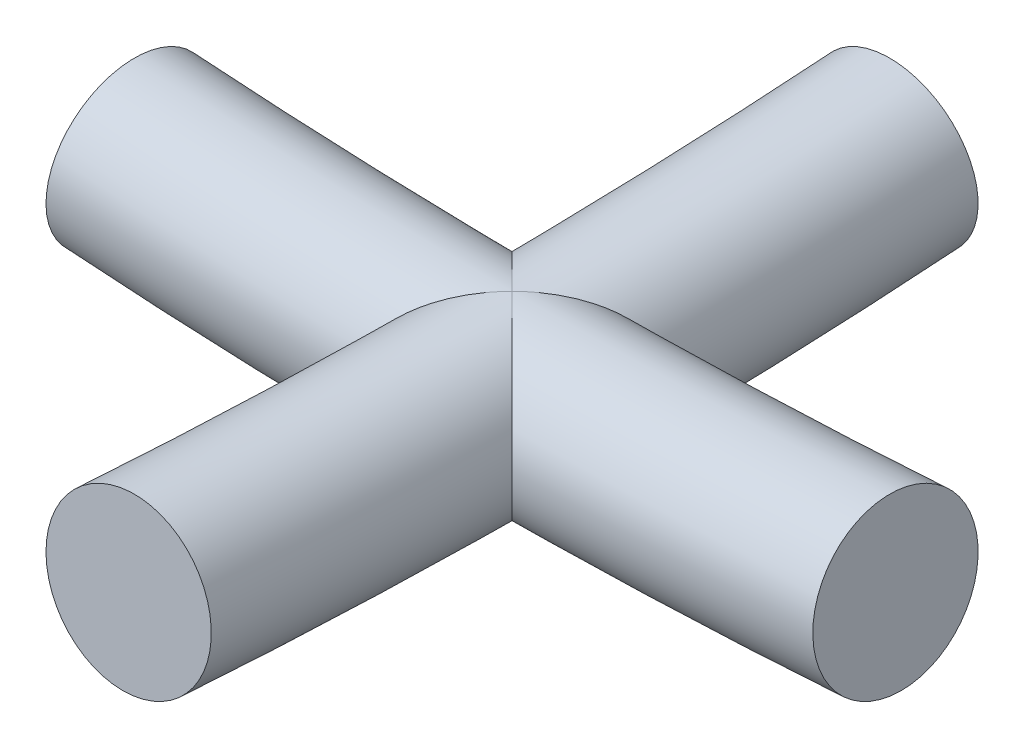
SolidWorks part; units mm, degrees
note: '?' marks a value the reader was unsure of.
ref_plane "Front Plane" through (0, 0, 0) normal (0, 0, 1) x (1, 0, 0)
ref_plane "Top Plane" through (0, 0, 0) normal (0, 1, 0) x (1, 0, 0)
ref_plane "Right Plane" through (0, 0, 0) normal (1, 0, 0) x (0, 0, -1)
sketch "Sketch3" plane through (0, 0, 0) normal (0, 0, 1) x (1, 0, 0)
  line L0 (0, 0) -> (0, -500) construction
  circle A0 centre (0, -500) radius 7.5
  dimension "D2" = 15
  dimension "D1" = 500
ref_axis "Axis1" through (8.6893, 0, 0) along (-1, 0, 0)?
revolve "Revolve1" add sketch "Sketch3" angle 4 about axis through (8.6893, 0, 0) along (-1, 0, 0)
sketch "Sketch4" plane through (0, 0, 0) normal (1, 0, 0) x (0, 0, -1)
  line L0 (0, 0) -> (0, -500) construction
  circle A0 centre (0, -500) radius 7.5
  dimension "D1" = 15
  dimension "D2" = 500
ref_axis "Axis2" through (0, 0, -38.9722) along (0, 0, 1)?
revolve "Revolve2" add sketch "Sketch4" angle 4 about axis through (0, 0, -38.9722) along (0, 0, 1)
